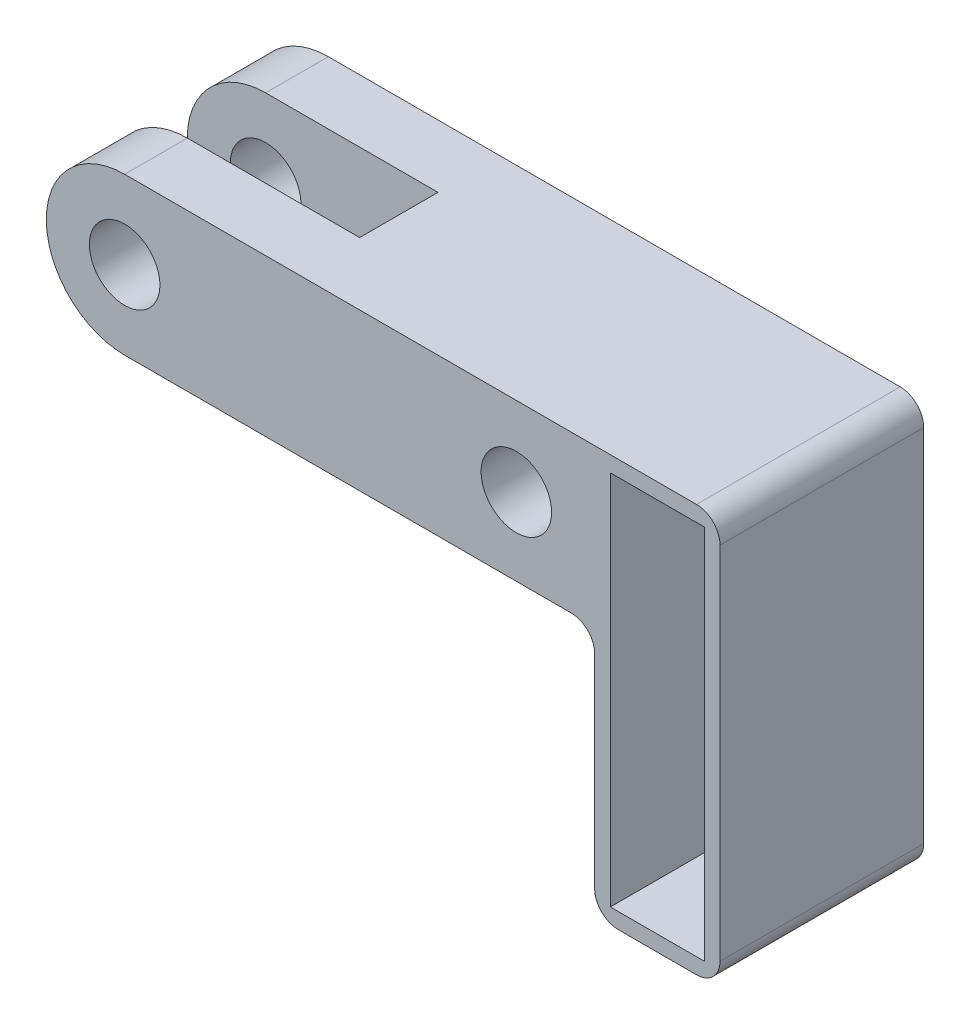
SolidWorks part; units mm, degrees
ref_plane "Front Plane" through (0, 0, 0) normal (0, 0, 1) x (1, 0, 0)
ref_plane "Top Plane" through (0, 0, 0) normal (0, 1, 0) x (1, 0, 0)
ref_plane "Right Plane" through (0, 0, 0) normal (1, 0, 0) x (0, 0, -1)
sketch "Sketch1" plane through (0, 0, 0) normal (0, 0, 1) x (1, 0, 0)
  line L0 (0, -5) -> (30, -5)
  line L1 (0, 5) -> (38, 5)
  line L10 (38, 5) -> (38, -21)
  line L11 (38, -21) -> (30, -21)
  line L12 (30, -5) -> (30, -21)
  line L14 (31, -20) -> (37, -20)
  line L15 (31, -20) -> (31, 4)
  line L16 (31, 4) -> (37, 4)
  line L17 (37, -20) -> (37, 4)
  arc A0 (0, 5) -> (0, -5) centre (0, 0) ccw
  circle A2 centre (0, 0) radius 2.25
  circle A4 centre (25, -0.0668) radius 2.25
  dimension "D1" = 5
  dimension "D3" = 4.5
  dimension "D11" = 4.5
  dimension "D2" = 30
  dimension "D4" = 1
  dimension "D5" = 1
  dimension "D6" = 1
  dimension "D7" = 6
  dimension "D8" = 24
  dimension "D9" = 1
  dimension "D10" = 6
extrude "Boss-Extrude1" add sketch "Sketch1" along normal mid plane 13 contours L1 A0 A2 region at (16.6775, -1.3755, 0)
sketch "Sketch13" plane through (0, -5, 0) normal (0, -1, 0) x (1, 0, 0)
  line L0 (-5, 6.5) -> (-5, -6.5) construction
  line L1 (-5, -2.5) -> (11, -2.5)
  line L2 (-5, -2.5) -> (-5, 2.5)
  line L3 (-5, 2.5) -> (11, 2.5)
  line L4 (11, -2.5) -> (11, 2.5)
  point P6 (-5, 0)
  dimension "D1" = 5
  dimension "D2" = 16
extrude "Cut-Extrude1" cut sketch "Sketch13" against normal blind 10
chamfer "Chamfer1" distance 8 distance2 10 1 edges at (11, -5, 0) tangent propagation no first distance on face at (10.25, -5, 0)
fillet "Fillet1" radius 1.5 4 edges at (30, -5, 0) (38, 5, 0) (38, -21, 0) (30, -21, 0)
